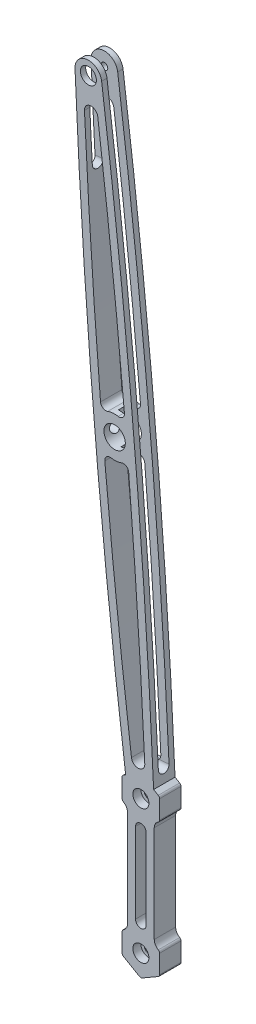
SolidWorks part; units mm, degrees
material "A2017"
ref_plane "正面" through (0, 0, 0) normal (0, 0, 1) x (1, 0, 0)
ref_plane "平面" through (0, 0, 0) normal (0, 1, 0) x (1, 0, 0)
ref_plane "右側面" through (0, 0, 0) normal (1, 0, 0) x (0, 0, -1)
sketch "ｽｹｯﾁ1" plane through (0, 0, 0) normal (0, 0, 1) x (1, 0, 0)
  line L0 (0, 0) -> (9.0749, 0) construction
  line L1 (0, 25) -> (0, 0) construction
  line L2 (0, -16.9171) -> (7, -20.9585)
  line L3 (7, 20.9585) -> (7, 29.0415)
  line L4 (7, 29.0415) -> (0, 33.0829)
  line L5 (0, 33.0829) -> (-7, 29.0415)
  line L6 (-7, 29.0415) -> (-7, 20.9585)
  line L7 (-7, 20.9585) -> (0, 16.9171)
  line L8 (0, 16.9171) -> (7, 20.9585)
  line L9 (-7, -20.9585) -> (0, -16.9171)
  line L10 (-7, -29.0415) -> (-7, -20.9585)
  line L11 (0, -33.0829) -> (-7, -29.0415)
  line L12 (7, -29.0415) -> (0, -33.0829)
  line L13 (7, -20.9585) -> (7, -29.0415)
  circle A0 centre (0, 25) radius 3
  circle A1 centre (0, -25) radius 3
  circle A2 centre (0, 25) radius 7 construction
  circle A3 centre (0, -25) radius 7 construction
  dimension "D1" = 6
  dimension "D2" = 50
  dimension "D3" = 14
extrude "ﾎﾞｽ - 押し出し1" add sketch "ｽｹｯﾁ1" along normal mid plane 8
sketch "ｽｹｯﾁ2" plane through (0, 0, 4) normal (0, 0, 1) x (1, 0, 0)
  line L0 (-7, 20.9585) -> (0, 16.9171) construction
  line L1 (5, -19.8038) -> (-5, -19.8038)
  line L2 (5, -19.8038) -> (5, 19.8038)
  line L3 (5, 19.8038) -> (-5, 19.8038)
  line L4 (-5, -19.8038) -> (-5, 19.8038)
  line L5 (5, -19.8038) -> (-5, 19.8038) construction
  line L6 (5, 19.8038) -> (-5, -19.8038) construction
  point P0 (0, 0)
  dimension "D1" = 10
extrude "ﾎﾞｽ - 押し出し2" add sketch "ｽｹｯﾁ2" against normal up to surface (8 mm away) up to face at (0, 25, -4)
fillet "ﾌｨﾚｯﾄ1" radius 3 4 edges at (5, -19.8038, 0) (-5, 19.8038, 0) (-5, -19.8038, 0) (5, 19.8038, 0)
fillet "ﾌｨﾚｯﾄ2" radius 1 10 edges at (-7, 20.9585, 0) (-7, 29.0415, 0) (0, 33.0829, 0) (7, 29.0415, 0) (7, 20.9585, 0) (7, -29.0415, 0) (0, -33.0829, 0) (-7, -29.0415, 0) (-7, -20.9585, 0) (7, -20.9585, 0)
sketch "ｽｹｯﾁ3" plane through (0, 0, -4) normal (0, 0, -1) x (-1, 0, 0)
  line L0 (0, -15) -> (0, 15) construction
  line L1 (-2, -15) -> (-2, 15)
  line L2 (2, -15) -> (2, 15)
  arc A0 (-2, -15) -> (2, -15) centre (0, -15) ccw
  arc A1 (2, 15) -> (-2, 15) centre (0, 15) ccw
  point P2 (0, 0)
  dimension "D1" = 4
  dimension "D2" = 30
extrude "ｶｯﾄ - 押し出し1" cut sketch "ｽｹｯﾁ3" against normal up to surface (8 mm away) up to face at (0, 0, 4)
sketch "ｽｹｯﾁ5" plane through (0, 0, 4) normal (0, 0, 1) x (1, 0, 0)
  circle A0 centre (0, -25) radius 3 construction
  circle A1 centre (0, 25) radius 3 construction
  circle A2 centre (0, -25) radius 3
  circle A3 centre (0, 25) radius 3
extrude "ﾎﾞｽ - 押し出し3" [suppressed] add sketch "ｽｹｯﾁ5" against normal blind 5
sketch "ｽｹｯﾁ8" plane through (0, 0, -4) normal (0, 0, -1) x (-1, 0, 0)
  circle A0 centre (0, -25) radius 3 construction
  circle A1 centre (0, 25) radius 3 construction
  circle A2 centre (0, -25) radius 3
  circle A3 centre (0, 25) radius 3
extrude "ﾎﾞｽ - 押し出し4" add sketch "ｽｹｯﾁ8" against normal blind 5
hole_wizard "M3 すきま穴1" positions "ｽｹｯﾁ6" profile "ｽｹｯﾁ7" hole size "M3" standard "JIS" end condition through all
sketch "ｽｹｯﾁ6" plane through (0, 0, 4) normal (0, 0, -1) x (-1, 0, 0)
  point P0 (0, 25)
  point P3 (0, -25)
sketch "ｽｹｯﾁ7" plane through (0, 25, 4) normal (1, 0, 0) x (0, -1, 0)
  line L0 (0, 0) -> (0, 8)
  line L1 (0, 8) -> (1.7, 8)
  line L2 (1.7, 8) -> (1.7, 0)
  line L5 (1.7, 0) -> (0, 0)
  line L11 (0, -6.35) -> (0, 107.95) construction
  dimension "通し穴の直径" = 3.4
  dimension "通し穴の深さ" = 8
sketch "ｽｹｯﾁ9" plane through (0, 0, 4) normal (0, 0, 1) x (1, 0, 0)
  line L0 (0, 25) -> (0, 298.9535) construction
  line L1 (0, 25) -> (-19.61, 249.1438) construction
  line L2 (0, 25) -> (-19.61, 249.1438) construction
  line L3 (-7.4715, 24.3463) -> (-27.0815, 248.4901) construction
  line L4 (7.4715, 25.6537) -> (-12.1386, 249.7975) construction
  line L15 (-7, 28.4641) -> (-7, 21.5359)
  line L16 (-5, 18.0718) -> (-5, -18.0718)
  line L17 (-7, -21.5359) -> (-7, -28.4641)
  line L18 (-6.5, -29.3301) -> (-0.5, -32.7942)
  line L19 (0.5, -32.7942) -> (6.5, -29.3301)
  line L20 (7, -28.4641) -> (7, -21.5359)
  line L21 (5, -18.0718) -> (5, 18.0718)
  line L22 (7, 21.5359) -> (7, 28.4641)
  line L23 (6.5, 29.3301) -> (0.5, 32.7942)
  line L24 (-0.5, 32.7942) -> (-6.5, 29.3301)
  line L25 (-7, 28.4641) -> (-7, 21.5359)
  line L26 (-5, 18.0718) -> (-5, -18.0718)
  line L27 (-7, -21.5359) -> (-7, -28.4641)
  line L28 (-6.5, -29.3301) -> (-0.5, -32.7942)
  line L29 (0.5, -32.7942) -> (6.5, -29.3301)
  line L30 (7, -28.4641) -> (7, -21.5359)
  line L31 (5, -18.0718) -> (5, 18.0718)
  line L32 (7, 21.5359) -> (7, 28.4641)
  line L33 (6.5, 29.3301) -> (0.5, 32.7942)
  line L34 (-0.5, 32.7942) -> (-6.5, 29.3301)
  arc A0 (-7.4715, 24.3463) -> (7.4715, 25.6537) centre (0, 25) ccw construction
  arc A1 (-12.1386, 249.7975) -> (-27.0815, 248.4901) centre (-19.61, 249.1438) ccw construction
  circle A2 centre (-19.61, 249.1438) radius 5 construction
  circle A3 centre (0, 25) radius 5
  arc A4 (-14.6533, 249.8004) -> (4.9954, 25.2141) centre (-2530.1776, -83.4321) cw
  arc A5 (-24.6055, 248.9297) -> (-4.9567, 24.3434) centre (2510.5676, 357.5759) ccw
  arc A6 (-14.6533, 249.8004) -> (-24.6055, 248.9297) centre (-19.61, 249.1438) ccw
  arc A16 (-7, 21.5359) -> (-6.5, 20.6699) centre (-6, 21.5359) ccw
  arc A17 (-5, 18.0718) -> (-6.5, 20.6699) centre (-8, 18.0718) ccw
  arc A18 (-6.5, -20.6699) -> (-5, -18.0718) centre (-8, -18.0718) ccw
  arc A19 (-6.5, -20.6699) -> (-7, -21.5359) centre (-6, -21.5359) ccw
  arc A20 (-7, -28.4641) -> (-6.5, -29.3301) centre (-6, -28.4641) ccw
  arc A21 (-0.5, -32.7942) -> (0.5, -32.7942) centre (0, -31.9282) ccw
  arc A22 (6.5, -29.3301) -> (7, -28.4641) centre (6, -28.4641) ccw
  arc A23 (7, -21.5359) -> (6.5, -20.6699) centre (6, -21.5359) ccw
  arc A24 (5, -18.0718) -> (6.5, -20.6699) centre (8, -18.0718) ccw
  arc A25 (6.5, 20.6699) -> (5, 18.0718) centre (8, 18.0718) ccw
  arc A26 (6.5, 20.6699) -> (7, 21.5359) centre (6, 21.5359) ccw
  arc A27 (7, 28.4641) -> (6.5, 29.3301) centre (6, 28.4641) ccw
  arc A28 (0.5, 32.7942) -> (-0.5, 32.7942) centre (0, 31.9282) ccw
  arc A29 (-6.5, 29.3301) -> (-7, 28.4641) centre (-6, 28.4641) ccw
  arc A30 (-7, 21.5359) -> (-6.5, 20.6699) centre (-6, 21.5359) ccw
  arc A31 (-5, 18.0718) -> (-6.5, 20.6699) centre (-8, 18.0718) ccw
  arc A32 (-6.5, -20.6699) -> (-5, -18.0718) centre (-8, -18.0718) ccw
  arc A33 (-6.5, -20.6699) -> (-7, -21.5359) centre (-6, -21.5359) ccw
  arc A34 (-7, -28.4641) -> (-6.5, -29.3301) centre (-6, -28.4641) ccw
  arc A35 (-0.5, -32.7942) -> (0.5, -32.7942) centre (0, -31.9282) ccw
  arc A36 (6.5, -29.3301) -> (7, -28.4641) centre (6, -28.4641) ccw
  arc A37 (7, -21.5359) -> (6.5, -20.6699) centre (6, -21.5359) ccw
  arc A38 (5, -18.0718) -> (6.5, -20.6699) centre (8, -18.0718) ccw
  arc A39 (6.5, 20.6699) -> (5, 18.0718) centre (8, 18.0718) ccw
  arc A40 (6.5, 20.6699) -> (7, 21.5359) centre (6, 21.5359) ccw
  arc A41 (7, 28.4641) -> (6.5, 29.3301) centre (6, 28.4641) ccw
  arc A42 (0.5, 32.7942) -> (-0.5, 32.7942) centre (0, 31.9282) ccw
  arc A43 (-6.5, 29.3301) -> (-7, 28.4641) centre (-6, 28.4641) ccw
  point P4 (-9.805, 137.0719)
  arc M28 (0.5, 32.7942) -> (-0.5, 32.7942) centre (0, 31.9282) ccw
  line M29 (-0.5, 32.7942) -> (-6.5, 29.3301)
  dimension "D5" = 10
  dimension "D1" = 5
  dimension "D2" = 225
  dimension "D4" = 15
  dimension "D3" = 0
extrude "ﾎﾞｽ - 押し出し5" add sketch "ｽｹｯﾁ9" against normal up to surface (8 mm away) contours A4 A6 A5 L33 M29 M28 region at (-10.1534, 141.0541, 4) up to face at (1.7, 25, -4)
sketch "ｽｹｯﾁ12" plane through (0, 0, -4) normal (0, 0, -1) x (-1, 0, 0)
  line L0 (19.61, 249.1438) -> (0, 25) construction
hole_wizard "M3 ねじ穴1" positions "ｽｹｯﾁ19" profile "ｽｹｯﾁ20" tap size "M3" standard "JIS" end condition through all
sketch "ｽｹｯﾁ19" plane through (0, 0, 4) normal (0, 0, 1) x (1, 0, 0)
  point P0 (-19.61, 249.1438)
sketch "ｽｹｯﾁ20" plane through (-19.61, 249.1438, 4) normal (1, 0, 0) x (0, -1, 0)
  line L0 (0, 0) -> (0, 8)
  line L1 (0, 8) -> (1.25, 8)
  line L2 (1.25, 8) -> (1.25, 0)
  line L5 (1.25, 0) -> (0, 0)
  line L11 (0, -6.35) -> (0, 107.95) construction
  dimension "次ｻｰﾌｪｽまでのねじ下穴ﾄﾞﾘﾙ直径" = 2.5
  dimension "次ｻｰﾌｪｽまでのねじ下穴ﾄﾞﾘﾙの深さ" = 8
cosmetic thread "穴のねじ山1" parameters "D2"=3
sketch "ｽｹｯﾁ10" plane through (0, 0, 4) normal (0, 0, 1) x (1, 0, 0)
  circle A0 centre (-19.61, 249.1438) radius 3
  dimension "D1" = 6
extrude "ｶｯﾄ - 押し出し2" cut sketch "ｽｹｯﾁ10" against normal blind 6
sketch "ｽｹｯﾁ21" plane through (0, 0, -4) normal (0, 0, -1) x (-1, 0, 0)
  circle A0 centre (19.61, 249.1438) radius 3
  dimension "D1" = 6
extrude "ｶｯﾄ - 押し出し8" [suppressed] cut sketch "ｽｹｯﾁ21" against normal blind 6
ref_plane "平面1" through (2.1706, 0.1899, 0) normal (0.9962, 0.0872, 0) x (0.0872, -0.9962, 0)
sketch "ｽｹｯﾁ13" plane through (0, 0, -4) normal (0, 0, -1) x (-1, 0, 0)
  line L0 (19.61, 249.1438) -> (0, 25) construction
  arc A2 (17.6274, 249.4065) -> (-1.7741, 30.1938) centre (2530.1776, -83.4321) ccw
  arc A3 (17.6274, 249.4065) -> (-1.7741, 30.1938) centre (2530.1776, -83.4321) ccw
  arc A4 (21.0716, 237.1884) -> (16.0946, 237.6238) centre (18.5745, 237.3071) ccw
  arc A5 (2.6995, 30.1943) -> (21.6082, 249.0582) centre (-2510.5676, 357.5759) ccw
  arc A6 (2.6995, 30.1943) -> (21.6082, 249.0582) centre (-2510.5676, 357.5759) ccw
  arc A7 (-1.4616, 36.9554) -> (3.5154, 36.52) centre (1.0356, 36.8367) ccw
  dimension "D3" = 5
  dimension "D1" = 3
  dimension "D2" = 3
extrude "ｶｯﾄ - 押し出し3" cut sketch "ｽｹｯﾁ13" against normal through all contours A3 A7 A6 A4 region at (-9.805, 137.0719, -4)
sketch "ｽｹｯﾁ14" plane through (0, 0, -4) normal (0, 0, -1) x (-1, 0, 0)
  line L0 (14.2879, 136.6797) -> (5.3221, 137.4641) construction
  arc A0 (3.5154, 36.52) -> (21.0716, 237.1884) centre (-2510.5676, 357.5759) ccw construction
  arc A1 (16.0946, 237.6238) -> (-1.4616, 36.9554) centre (2530.1776, -83.4321) ccw construction
  circle A2 centre (9.805, 137.0719) radius 7.5
  arc A3 (5.6744, 29.8068) -> (24.6055, 248.9297) centre (-2510.5676, 357.5759) ccw construction
extrude "ﾎﾞｽ - 押し出し6" add sketch "ｽｹｯﾁ14" against normal up to surface (8 mm away) up to face at (-9.805, 137.0719, 4)
fillet "ﾌｨﾚｯﾄ3" radius 2 4 edges at (-4.8058, 131.481, 0) (-13.7574, 130.6978, 0) (-14.8042, 142.6628, 0) (-5.8526, 143.446, 0)
sketch "ｽｹｯﾁ15" plane through (0, 0, 4) normal (0, 0, 1) x (1, 0, 0)
  line L0 (-19.61, 249.1438) -> (0, 25) construction
  circle A0 centre (-9.805, 137.0719) radius 4
  dimension "D1" = 8
extrude "ｶｯﾄ - 押し出し4" cut sketch "ｽｹｯﾁ15" against normal through all
sketch "ｽｹｯﾁ16" plane through (2.1706, 0.1899, 0) normal (0.9962, 0.0872, 0) x (0.0872, -0.9962, 0)
  line L0 (-254.9049, 0) -> (-34.9049, 0) construction
  line L1 (-254.9049, 4) -> (-254.9049, -4) construction
  line L2 (-254.9049, 2) -> (-34.9049, 2)
  line L3 (-254.9049, -2) -> (-34.9049, -2)
  arc A0 (-254.9049, 2) -> (-254.9049, -2) centre (-254.9049, 0) ccw
  arc A1 (-34.9049, -2) -> (-34.9049, 2) centre (-34.9049, 0) ccw
  point P5 (-144.9049, 0)
  dimension "D1" = 4
  dimension "D2" = 220
extrude "ｶｯﾄ - 押し出し6" cut sketch "ｽｹｯﾁ16" along normal through all
sketch "ｽｹｯﾁ22" plane through (2.1706, 0.1899, 0) normal (0.9962, 0.0872, 0) x (0, 0, -1)
  line L0 (0, 254.9049) -> (0, 219.9049) construction
  line L1 (-2, 254.9049) -> (2, 254.9049) construction
  line L2 (2, 254.9049) -> (2, 219.9049)
  line L3 (-2, 254.9049) -> (-2, 219.9049)
  line L4 (2, 252.9049) -> (2, 254.9049) construction
  arc A0 (2, 254.9049) -> (-2, 254.9049) centre (0, 254.9049) ccw
  arc A1 (-2, 219.9049) -> (2, 219.9049) centre (0, 219.9049) ccw
  point P5 (0, 237.4049)
  dimension "D1" = 35
extrude "ｶｯﾄ - 押し出し9" cut sketch "ｽｹｯﾁ22" against normal through all
sketch "ｽｹｯﾁ23" plane through (2.1706, 0.1899, 0) normal (0.9962, 0.0872, 0) x (0, 0, -1)
  line L0 (0, 129.9049) -> (0, 144.9049) construction
  line L1 (2, 129.9049) -> (-2, 129.9049) construction
  line L2 (-2, 144.9049) -> (2, 144.9049) construction
  circle A0 centre (0, 137.4049) radius 2
  dimension "D1" = 4
extrude "ｶｯﾄ - 押し出し10" cut sketch "ｽｹｯﾁ23" against normal through all
